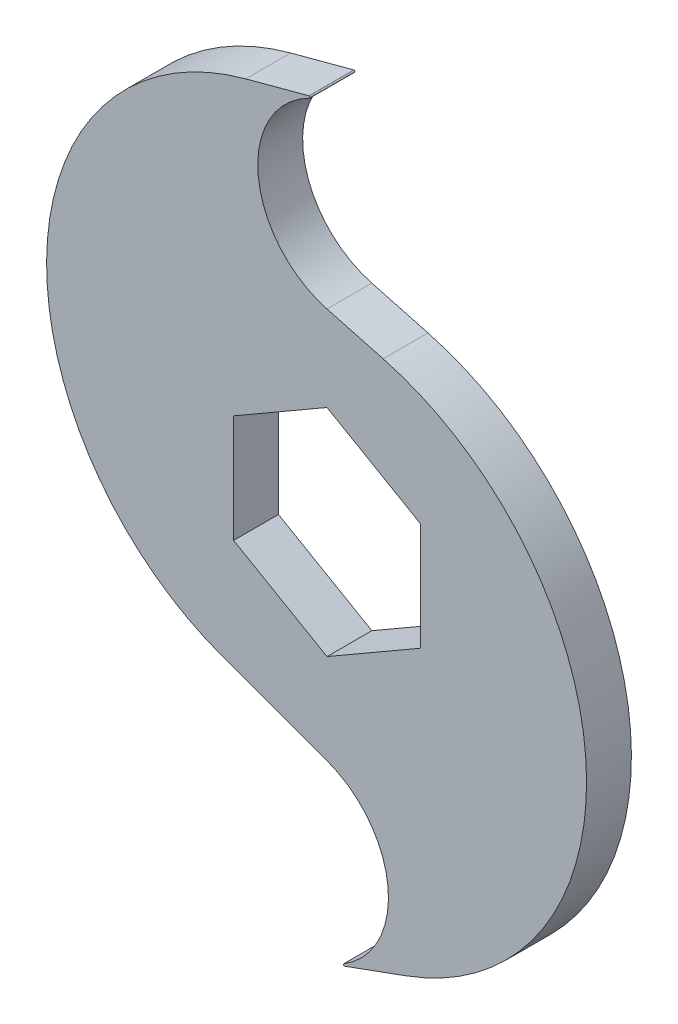
SolidWorks part; units mm, degrees
ref_plane "Front Plane" through (0, 0, 0) normal (0, 0, 1) x (1, 0, 0)
ref_plane "Top Plane" through (0, 0, 0) normal (0, 1, 0) x (1, 0, 0)
ref_plane "Right Plane" through (0, 0, 0) normal (1, 0, 0) x (0, 0, -1)
sketch "Sketch1" plane through (0, 0, 0) normal (0, 0, 1) x (1, 0, 0)
  line L0 (0, 50.8) -> (-11.0405, 47.8417)
  line L1 (0, 50.8) -> (0, 0) construction
  line L2 (0, -50.8) -> (10.7407, -46.8907)
  line L3 (0, 0) -> (0, -50.8) construction
  line L5 (0, 14.6647) -> (-12.7, 7.3323)
  line L6 (-12.7, 7.3323) -> (-12.7, -7.3323)
  line L7 (-12.7, -7.3323) -> (0, -14.6647)
  line L8 (0, -14.6647) -> (12.7, -7.3323)
  line L9 (12.7, -7.3323) -> (12.7, 7.3323)
  line L10 (12.7, 7.3323) -> (0, 14.6647)
  line L11 (0, 26.2655) -> (7.636, 24.2194)
  line L12 (0, -26.9318) -> (-14.0814, -21.8066)
  circle A0 centre (0, 0) radius 50.8 construction
  arc A1 (0, 50.8) -> (0, 26.2655) centre (3.287, 38.5327) ccw
  arc A3 (0, -50.8) -> (0, -26.9318) centre (-4.3437, -38.8659) ccw
  arc A4 (10.7407, -46.8907) -> (7.636, 24.2194) centre (-2.0222, -11.8251) ccw
  arc A5 (-11.0405, 47.8417) -> (-14.0814, -21.8066) centre (-1.581, 12.5382) ccw
  circle A6 centre (0, 0) radius 12.7 construction
  dimension "D4" = 70
  dimension "D5" = 25.4
  dimension "D1" = 101.6
  dimension "D6" = 12.7
  dimension "D2" = 11.43
  dimension "D3" = 75
extrude "Boss-Extrude1" add sketch "Sketch1" along normal mid plane 6.096
fillet "Fillet1" radius 0.127 2 edges at (0, 50.8, 0) (0, -50.8, 0)
